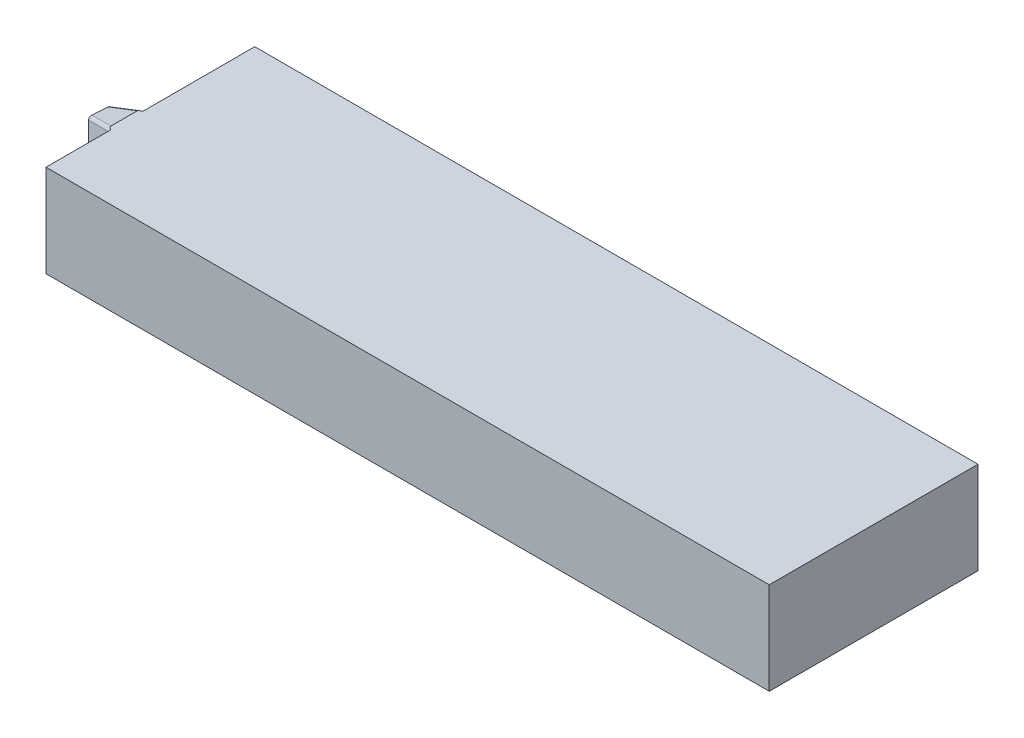
SolidWorks part; units mm, degrees
material "A-2 Steel"
ref_plane "Alzado" through (0, 0, 0) normal (0, 0, 1) x (1, 0, 0)
ref_plane "Planta" through (0, 0, 0) normal (0, 1, 0) x (1, 0, 0)
ref_plane "Vista lateral" through (0, 0, 0) normal (1, 0, 0) x (0, 0, -1)
sketch "Croquis1" plane through (0, 0, 0) normal (0, 1, 0) x (1, 0, 0)
  line L1 (11, 3.175) -> (-11, 3.175)
  line L2 (11, 3.175) -> (11, -3.175)
  line L3 (11, -3.175) -> (-11, -3.175)
  line L4 (-11, 3.175) -> (-11, -3.175)
  line L5 (0, -3.175) -> (0, 3.175) construction
  line L6 (11, 0) -> (-11, 0) construction
  point P124 (0, 0)
  dimension "D1" = 6.35
  dimension "D2" = 22
extrude "Saliente-Extruir1" add sketch "Croquis1" along normal blind 2.8067
sketch "Croquis2" plane through (-11, 0, 0) normal (-1, 0, 0) x (0, 0, 1)
  line L0 (1.5, 2.8067) -> (1.5, 0) construction
  line L1 (-3.175, 2.8067) -> (3.175, 2.8067) construction
  line L2 (-3.175, 0) -> (3.175, 0) construction
  line L3 (-1.5, 2.8067) -> (-1.5, 0) construction
  line L4 (-1.5, 1.4034) -> (1.5, 1.4034) construction
  line L5 (0, 0) -> (0, 1.4034) construction
  text T0 "4" font "Arial" height 3.0226
  dimension "D1" = 3
extrude "Saliente-Extruir2" add sketch "Croquis2" along normal blind 1.077
chamfer "Chaflán1" distance 1.077 angle 18 11 edges at (-11, 1.2871, 1.19) (-11, 1.8877, 0.88) (-11, 2.4884, 0.629) (-11, 1.8493, -0.5529) (-11, 0.958, -1.4838) (-11, 0.7058, -0.5538) (-11, 0.5121, 0.3762) (-11, 0.3183, 0.6281) (-11, 0.5121, 0.88) (-11, 0.7058, 1.19) (-11, 0.9965, 1.5) first distance on face at (-11.5385, 1.2871, 1.19) first distance on face at (-11.5385, 1.8877, 0.88) first distance on face at (-11.5385, 2.4884, 0.629) first distance on face at (-11.5385, 1.8493, -0.5529) first distance on face at (-11.5385, 0.958, -1.4838) first distance on face at (-11.5385, 0.7058, -0.5538) first distance on face at (-11.5385, 0.5121, 0.3762) first distance on face at (-11.5385, 0.3183, 0.6281) first distance on face at (-11.5385, 0.5121, 0.88) first distance on face at (-11.5385, 0.7058, 1.19) first distance on face at (-11.5385, 0.9965, 1.5)
chamfer "Chaflán2" distance 1.077 angle 8 3 edges at (-11, 1.6328, 0.3762) (-11, 1.2871, -0.1269) (-11, 1.6328, -0.1269) first distance on face at (-11.5385, 1.6328, 0.3762) first distance on face at (-11.5385, 1.2871, -0.1269) first distance on face at (-11.5385, 1.6328, -0.1269)
fillet "Redondeo1" radius 0.0992 14 edges at (-11.5385, 1.3628, -0.3863) (-11.5385, 1.3628, 0.3005) (-11.5385, 1.8347, 0.3005) (-11.5871, 2.6475, 0.3287) (-11.5871, 2.6475, 1.0391) (-11.5385, 1.4621, 1.0549) (-11.5385, 1.4621, 1.675) (-11.5385, 0.5309, 1.675) (-11.5385, 0.5309, 1.0549) (-11.5871, 0.1592, 1.0391) (-11.5871, 0.1592, 0.2171) (-11.5385, 0.5309, 0.2013) (-11.5385, 0.5309, -1.6588) (-11.5385, 1.3023, -1.6588)
sketch "Croquis3" plane through (0, 0, 0) normal (0, -1, 0) x (1, 0, 0)
  line L0 (-12.077, -1.4838) -> (-12.077, 1.5)
  arc A0 (-12.077, -1.4838) -> (-12.077, 1.5) centre (-18.2492, 0.0081) ccw
  dimension "D1" = 6.35
extrude "Cortar-Extruir1" cut sketch "Croquis3" against normal through all
